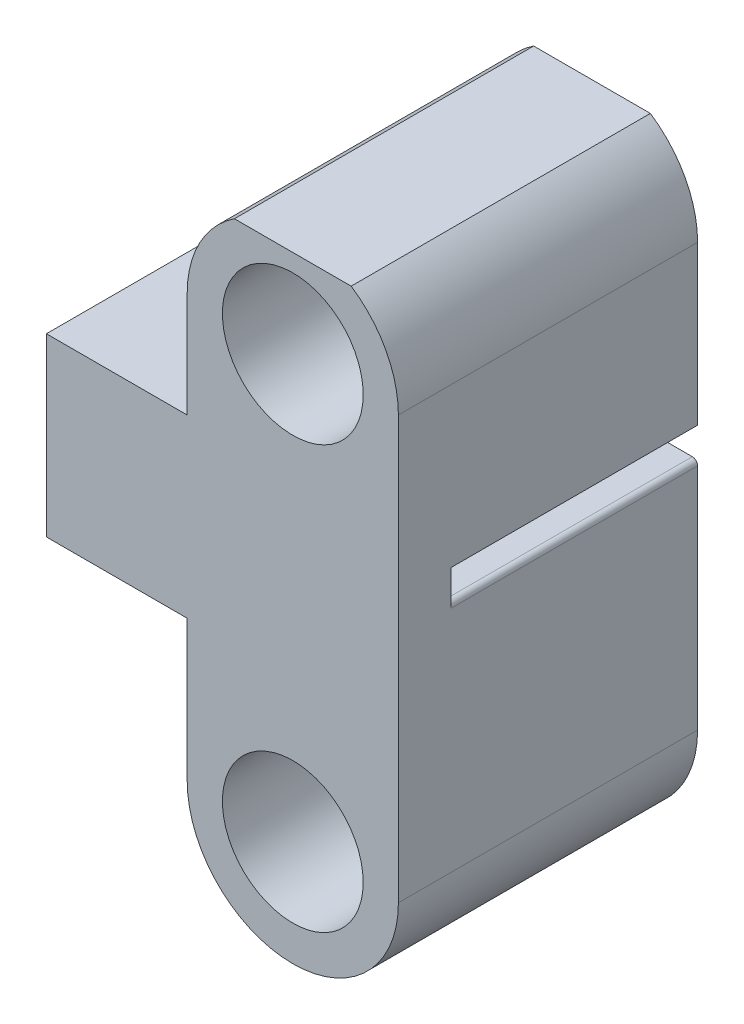
SolidWorks part; units mm, degrees
ref_plane "Front Plane" through (0, 0, 0) normal (0, 0, 1) x (1, 0, 0)
ref_plane "Top Plane" through (0, 0, 0) normal (0, 1, 0) x (1, 0, 0)
ref_plane "Right Plane" through (0, 0, 0) normal (1, 0, 0) x (0, 0, -1)
sketch "Sketch1" plane through (0, 0, 0) normal (0, 0, 1) x (1, 0, 0)
  line L0 (0, 0) -> (0, -12) construction
  line L1 (-3, 0) -> (-3, -12)
  line L2 (3, 0) -> (3, -12)
  arc A0 (3, 0) -> (-3, 0) centre (0, 0) ccw
  arc A1 (-3, -12) -> (3, -12) centre (0, -12) ccw
  circle A2 centre (0, 0) radius 2
  circle A3 centre (0, -12) radius 2
  dimension "D2" = 6
  dimension "D6" = 4
  dimension "D7" = 4
  dimension "D1" = 12
extrude "Boss-Extrude1" add sketch "Sketch1" along normal blind 8.5
sketch "Sketch2" plane through (3, 0, 0) normal (1, 0, 0) x (0, 0, -1)
  line L0 (-8.5, -6) -> (0, -6) construction
  line L1 (-8.5, -12) -> (-8.5, 0) construction
  line L2 (0, -12) -> (0, 0) construction
  line L3 (-4.25, 0) -> (-4.25, -12) construction
  line L4 (-8.5, 0) -> (0, 0) construction
  line L5 (-8.5, -12) -> (0, -12) construction
  circle A0 centre (-4.25, -8.5) radius 2
  dimension "D1" = 4
  dimension "D2" = 2.5
extrude "Cut-Extrude1" [suppressed] cut sketch "Sketch2" against normal through all
sketch "Sketch3" [suppressed] plane through (3, 0, 0) normal (1, 0, 0) x (0, 0, -1)
  line L1 (-0.6416, -8.5) -> (-2.4458, -5.375)
  line L2 (-2.4458, -5.375) -> (-6.0542, -5.375)
  line L3 (-6.0542, -5.375) -> (-7.8584, -8.5)
  line L4 (-7.8584, -8.5) -> (-6.0542, -11.625)
  line L5 (-6.0542, -11.625) -> (-2.4458, -11.625)
  line L6 (-2.4458, -11.625) -> (-0.6416, -8.5)
  line L7 (-1.8684, -4.375) -> (-6.6316, -4.375)
  line L8 (-6.6316, -4.375) -> (-9.0131, -8.5)
  line L9 (-9.0131, -8.5) -> (-6.6316, -12.625)
  line L10 (-6.6316, -12.625) -> (-1.8684, -12.625)
  line L11 (-1.8684, -12.625) -> (0.5131, -8.5)
  line L12 (0.5131, -8.5) -> (-1.8684, -4.375)
  circle A0 centre (-4.25, -8.5) radius 3.125 construction
  circle A1 centre (-4.25, -8.5) radius 4.125 construction
  dimension "D1" = 6.25
  dimension "D2" = 1
extrude "Boss-Extrude2" [suppressed] add sketch "Sketch3" along normal blind 2 and the other way blind 0.5
sketch "Sketch4" [suppressed] plane through (-3, 0, 0) normal (-1, 0, 0) x (0, 0, 1)
  line L0 (4.25, 0) -> (4.25, -6.5) construction
  line L1 (8.5, 0) -> (0, 0) construction
  line L3 (0.75, -2.75) -> (7.75, -2.75)
  line L4 (0.75, -2.75) -> (0.75, -5.75)
  line L5 (0.75, -5.75) -> (7.75, -5.75)
  line L6 (7.75, -2.75) -> (7.75, -5.75)
  line L7 (0.75, -2.75) -> (7.75, -5.75) construction
  line L8 (0.75, -5.75) -> (7.75, -2.75) construction
  circle A0 centre (4.25, -8.5) radius 2 construction
  point P7 (4.25, -4.25)
  dimension "D1" = 7
  dimension "D2" = 3
  dimension "D3" = 2.75
extrude "Cut-Extrude2" [suppressed] cut sketch "Sketch4" against normal through all
sketch "Sketch5" plane through (-3, 0, 0) normal (-1, 0, 0) x (0, 0, 1)
  line L0 (4.25, 0) -> (4.25, -12) construction
  line L1 (8.5, 0) -> (0, 0) construction
  line L2 (8.5, -12) -> (0, -12) construction
  line L3 (0, -6) -> (8.5, -6) construction
  line L4 (0, 0) -> (0, -12) construction
  line L5 (8.5, 0) -> (8.5, -12) construction
  line L7 (0, -15) -> (8.5, -15)
  line L8 (0, -15) -> (0, 3)
  line L9 (0, 3) -> (8.5, 3)
  line L10 (8.5, -15) -> (8.5, 3)
  line L11 (0, -15) -> (8.5, 3) construction
  line L12 (0, 3) -> (8.5, -15) construction
  point P12 (4.25, -6)
extrude "Cut-Extrude3" [suppressed] cut sketch "Sketch5" against normal through all flip side to cut
sketch "Sketch9" plane through (-3, 0, 0) normal (-1, 0, 0) x (0, 0, 1)
  line L0 (8.5, 0) -> (8.5, -12) construction
  line L1 (0, -3) -> (8.5, -3)
  line L2 (0, -3) -> (0, -8)
  line L3 (0, -8) -> (8.5, -8)
  line L4 (8.5, -3) -> (8.5, -8)
  line L5 (0, 0) -> (0, -12) construction
  line L6 (8.5, 0) -> (0, 0) construction
  dimension "D1" = 5
  dimension "D2" = 3
extrude "Boss-Extrude4" add sketch "Sketch9" along normal blind 4
sketch "Sketch6" plane through (3, 0, 0) normal (1, 0, 0) x (0, 0, -1)
  line L0 (0, -12) -> (0, 0) construction
  line L1 (0, -4.5) -> (-7, -4.5)
  line L2 (0, -4.5) -> (0, -6.1)
  line L3 (0, -6.1) -> (-7, -6.1)
  line L4 (-7, -4.5) -> (-7, -6.1)
  dimension "D1" = 1.6
  dimension "D2" = 4.5
  dimension "D3" = 7
extrude "Cut-Extrude5" cut sketch "Sketch6" against normal through all
sketch "Sketch7" plane through (0, 0, 7) normal (0, 0, -1) x (-1, 0, 0)
  line L0 (-3, -6.1) -> (-3, -5.5)
  line L1 (-3, -4.5) -> (-3, -6.1) construction
  line L2 (-2.85, -5.35) -> (-2.15, -5.35)
  line L3 (-2, -5.5) -> (-2, -6.1)
  line L4 (7, -6.1) -> (-3, -6.1) construction
  line L5 (-2, -6.1) -> (-3, -6.1)
  line L6 (-0.85, -5.35) -> (-0.15, -5.35)
  line L7 (0, -5.5) -> (0, -6.1)
  line L8 (0, -6.1) -> (-1, -6.1)
  line L9 (-1, -6.1) -> (-1, -5.5)
  line L10 (1.15, -5.35) -> (1.85, -5.35)
  line L11 (2, -5.5) -> (2, -6.1)
  line L12 (2, -6.1) -> (1, -6.1)
  line L13 (1, -6.1) -> (1, -5.5)
  line L14 (3.15, -5.35) -> (3.85, -5.35)
  line L15 (4, -5.5) -> (4, -6.1)
  line L16 (4, -6.1) -> (3, -6.1)
  line L17 (3, -6.1) -> (3, -5.5)
  line L18 (5.15, -5.35) -> (5.85, -5.35)
  line L19 (6, -5.5) -> (6, -6.1)
  line L20 (6, -6.1) -> (5, -6.1)
  line L21 (5, -6.1) -> (5, -5.5)
  arc A0 (-2.15, -5.35) -> (-2, -5.5) centre (-2.15, -5.5) cw
  arc A1 (-3, -5.5) -> (-2.85, -5.35) centre (-2.85, -5.5) cw
  arc A2 (-1, -5.5) -> (-0.85, -5.35) centre (-0.85, -5.5) cw
  arc A3 (-0.15, -5.35) -> (0, -5.5) centre (-0.15, -5.5) cw
  arc A4 (1, -5.5) -> (1.15, -5.35) centre (1.15, -5.5) cw
  arc A5 (1.85, -5.35) -> (2, -5.5) centre (1.85, -5.5) cw
  arc A6 (3, -5.5) -> (3.15, -5.35) centre (3.15, -5.5) cw
  arc A7 (3.85, -5.35) -> (4, -5.5) centre (3.85, -5.5) cw
  arc A8 (5, -5.5) -> (5.15, -5.35) centre (5.15, -5.5) cw
  arc A9 (5.85, -5.35) -> (6, -5.5) centre (5.85, -5.5) cw
  point P11 (-2, -5.35)
  point P14 (-3, -5.35)
  dimension "D3" = 0.15
  dimension "D1" = 1
  dimension "D2" = 0.75
  dimension "D4" = 5
extrude "Boss-Extrude3" add sketch "Sketch7" along normal through all
sketch "Sketch10" plane through (0, 0, 8.5) normal (0, 0, 1) x (1, 0, 0)
  line L1 (-2.5, 3.5) -> (2.5, 3.5)
  line L2 (-2.5, 3.5) -> (-2.5, 2.5)
  line L3 (-2.5, 2.5) -> (2.5, 2.5)
  line L4 (2.5, 3.5) -> (2.5, 2.5)
  line L5 (-2.5, 3.5) -> (2.5, 2.5) construction
  line L6 (-2.5, 2.5) -> (2.5, 3.5) construction
  arc A0 (3, 0) -> (-3, 0) centre (0, 0) ccw construction
  point P0 (0, 3)
  dimension "D1" = 1
  dimension "D2" = 5
extrude "Cut-Extrude6" cut sketch "Sketch10" against normal through all
equation "\"X-ROD-SPACING\"=45"
equation "\"Y-ROD-SPACING\"=75"
equation "\"Z-ROD-SPACING\"=17.5"
equation "\"Y-BED-OFFSET\"=2"
equation "\"Y-BED-ROD-INSET\"=3.5"
equation "\"Y-BED-SCREW-SPACING\"=209"
equation "\"Y-BED-SCREW-CUTOUT-SLOT-HEIGHT\"=2"
equation "\"T-SLOT-NUT-FILLET-RADIUS\"=0.5"
equation "\"T-SLOT-SCREW-SHAFT-RADIUS\"=1.55"
equation "\"T-SLOT-SCREW-SHAFT-CUTOUT-LENGTH\"=11"
equation "\"T-SLOT-NUT-DEPTH\"=3.5"
equation "\"T-SLOT-NUT-WIDTH\"=2.85"
equation "\"T-SLOT-NUT-END-DISTANCE\"=8"
equation "\"ACRYLIC-THICKNESS\"=10"
equation "\"ACRYLIC-THICKNESS2\"=4.5"
equation "\"ACRYLIC-TAB-CUTOUT-SIZE\"=\"ACRYLIC-THICKNESS\"+\"ACRYLIC-TAB-TOLERANCE\"*2"
equation "\"ACRYLIC-TAB-TOLERANCE\"=-.05"
equation "\"ACRYLIC-TAB-WIDTH\"=\"ACRYLIC-THICKNESS\""
equation "\"ACRYLIC-M3-HOLE\"=2.9"
equation "\"SMOOTHROD-CAP-SCREW-DISTANCE\"=20"
equation "\"FRAME-WIDTH-INNER\"=370"
equation "\"NEMA17-HOLE-SPACING\"=31"
equation "\"NEMA17-CENTRAL-CUTOUT\"=22.5"
equation "\"Z-BRACKET-REACH\"=57"
equation "\"Z-ROD-INSET\"=13.5"
equation "\"TOP-BRACKET-SPACING\"=40"
equation "\"SMOOTHROD-X-LENGTH\"=350"
equation "\"SMOOTHROD-Y-LENGTH\"=350"
equation "\"SMOOTHROD-Z-LENGTH\"=350"
equation "\"SMOOTHROD-TIGHTENING-HEADROOM\"=.25"
equation "\"LEADSCREW-Z-LENGTH\"=300"
equation "\"SCREW-LENGTH-FRAME\"=\"ACRYLIC-THICKNESS\" + 10"
equation "\"SCREW-LENGTH-MOTOR\"=\"ACRYLIC-THICKNESS\" + 5"
equation "\"SCREW-LENGTH-EXTRUDER\"=28"
equation "\"SCREW-HEAD-RADIUS\"=6"
equation "\"PRINTED-M3-HOLE\"=3.5"
equation "\"PRINTED-X-SMOOTHROD-DIAMETER\"=8.8"
equation "\"PRINTED-X-SMOOTHROD-CUTOUT\"=10"
equation "\"PRINTED-X-BASE-HEIGHT\"=10"
equation "\"PRINTED-LM8UU-CUTOUT-SIZE\"=15.5"
equation "\"PRINTED-LM8UU-CUTOUT-LENGTH\"=24.5"
equation "\"PRINTED-X-IDLER-HEIGHT\"=16"
equation "\"PRINTED-M3-NUT-AF\"=6.25"
equation "\"PSU-MOUNTING-WIDTH\"=95"
equation "\"PSU-MOUNTING-HEIGHT\"=177"
equation "\"Y-BELT-TO-ROD-DISTANCE\"=20"
equation "\"SPOOL-HOLDER-ROD-SPACING\"=150"
equation "\"ACRYLIC-X-CARRIAGE-WIDTH\"=55"
equation "\"ACRYLIC-X-CARRIAGE-HEIGHT\"=75"
equation "\"ACRYLIC-X-CARRIAGE-LM8UU-CUTOUT-WIDTH\"=24.25"
equation "\"ACRYLIC-X-CARRIAGE-LM8UU-CUTOUT-HEIGHT\"=11.0"
equation "\"ACRYLIC-X-CARRIAGE-SCREW-SPACING-X\"=15"
equation "\"ACRYLIC-X-CARRIAGE-SCREW-SPACING-Y\"=33"
equation "\"ACRYLIC-X-CARRIAGE-CENTER-TAB-SPACING\"=14"
equation "\"ACRYLIC-X-CARRIAGE-EXTRUDER-OFFSET\"=26"
equation "\"ACRYLIC-X-CARRIAGE-EXTRUDER-ANGLE\"=90"
equation "\"ACRYLIC-X-CARRIAGE-EXTRUDER-SHELF-DEPTH\"=\"ACRYLIC-X-CARRIAGE-EXTRUDER-OFFSET\" + 28"
equation "\"ACRYLIC-X-CARRIAGE-EXTRUDER-BRACE-SPACING\"=23"
equation "\"ACRYLIC-X-CARRIAGE-EXTRUDER-BRACE-TAB-OFFSET\"=20"
equation "\"ACRYLIC-X-CARRIAGE-EXTRUDER-BRACE-HEIGHT\"=35"
equation "\"ACRYLIC-X-CARRIAGE-EXTRUDER-BRACE-SCREW-SPACING\"=22"
equation "\"ACRYLIC-X-CARRIAGE-DUAL-WIDTH-MULTIPLIER\"=1.65"
equation "\"ACRYLIC-X-CARRIAGE-DUAL-HOTEND-SPACING\"=42"
equation "\"ACRYLIC-X-CARRIAGE-DUAL-WIDTH\"=75"
equation "\"ACRYLIC-X-CARRIAGE-DUAL-HOTEND-SEPARATION\"=36"
equation "\"ACRYLIC-X-CARRIAGE-DUAL-MOUNT-PLATE-DEPTH\"=75"
equation "\"ACRYLIC-X-CARRIAGE-DUAL-MOUNT-BRACE-WIDTH\"=33"
equation "\"ACRYLIC-X-CARRIAGE-DUAL-MOUNT-SCREW-WIDTH\"=40"
equation "\"BLOWER-FAN-WIDTH\"=15"
equation "\"D1@Sketch3\"=\"PRINTED-M3-NUT-AF\""
